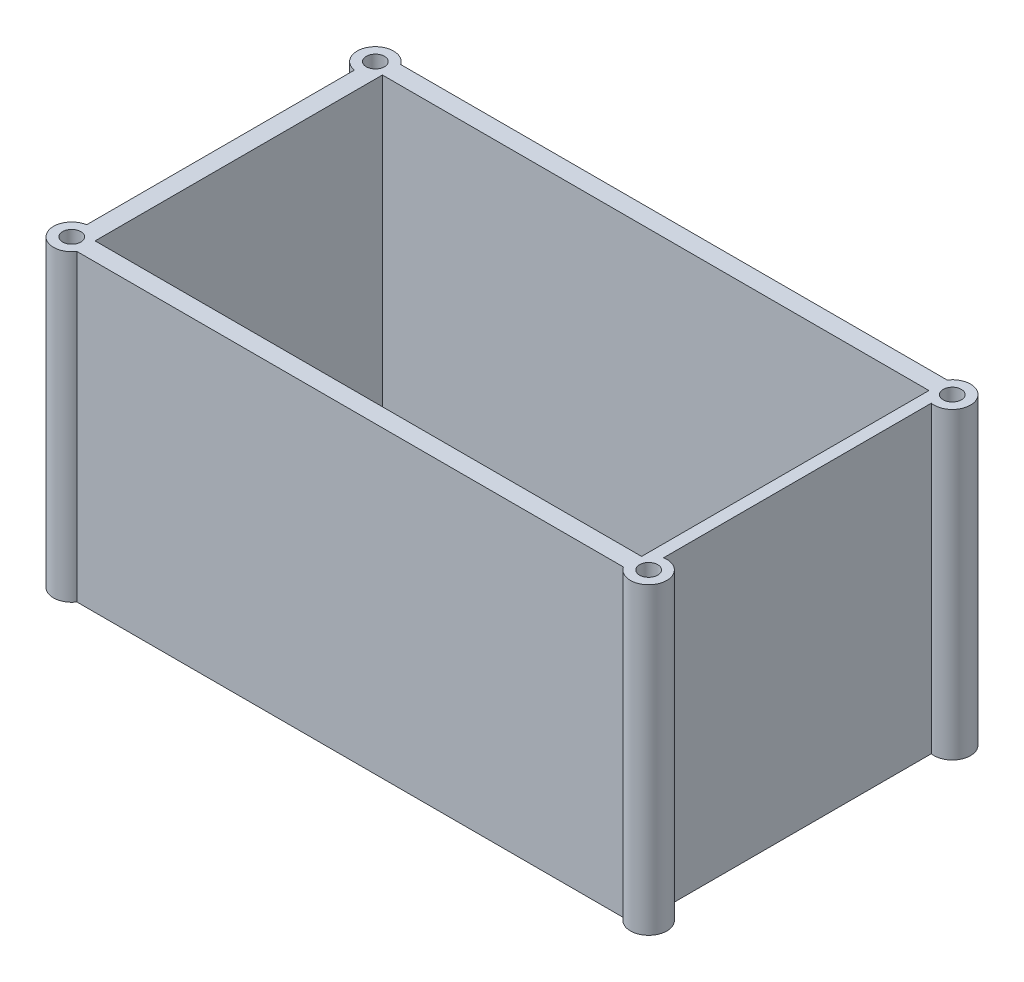
SolidWorks part; units mm, degrees
ref_plane "Front Plane" through (0, 0, 0) normal (0, 0, 1) x (1, 0, 0)
ref_plane "Top Plane" through (0, 0, 0) normal (0, 1, 0) x (1, 0, 0)
ref_plane "Right Plane" through (0, 0, 0) normal (1, 0, 0) x (0, 0, -1)
sketch "Sketch1" plane through (0, 0, 0) normal (0, 1, 0) x (1, 0, 0)
  line L0 (0, -26.6583) -> (0, 26.6583) construction
  line L1 (-45, 26.6583) -> (45, 26.6583)
  line L2 (-48, 22.042) -> (-48, -22.042)
  line L3 (-45, -26.6583) -> (45, -26.6583)
  line L4 (47, 22.042) -> (47, -22.042)
  line L5 (-47.5, 25) -> (47.5, -25) construction
  line L6 (-47.5, -25) -> (47.5, 25) construction
  line L7 (-48, 0) -> (47, 0) construction
  line L9 (-45, 23.6583) -> (45, 23.6583)
  line L10 (-45, 23.6583) -> (-45, -23.6583)
  line L11 (-45, -23.6583) -> (45, -23.6583)
  line L12 (45, 23.6583) -> (45, -23.6583)
  line L13 (-45, 23.6583) -> (45, -23.6583) construction
  line L14 (-45, -23.6583) -> (45, 23.6583) construction
  arc A0 (-48, -22.042) -> (-45, -26.6583) centre (-47.5, -25) ccw
  arc A1 (-45, 26.6583) -> (-48, 22.042) centre (-47.5, 25) ccw
  arc A2 (45, -26.6583) -> (47, -22.042) centre (47.5, -25) ccw
  arc A3 (47, 22.042) -> (45, 26.6583) centre (47.5, 25) ccw
  circle A4 centre (47.5, -25) radius 1.5
  circle A5 centre (-47.5, -25) radius 1.5
  circle A6 centre (47.5, 25) radius 1.5
  circle A7 centre (-47.5, 25) radius 1.5
  point P0 (0, 0)
  point P23 (0, 0)
  dimension "D3" = 3
  dimension "D4" = 90
  dimension "D5" = 3
  dimension "D1" = 95
  dimension "D2" = 50
  dimension "D9" = 3
  dimension "D10" = 3
extrude "Boss-Extrude1" add sketch "Sketch1" along normal blind 50
